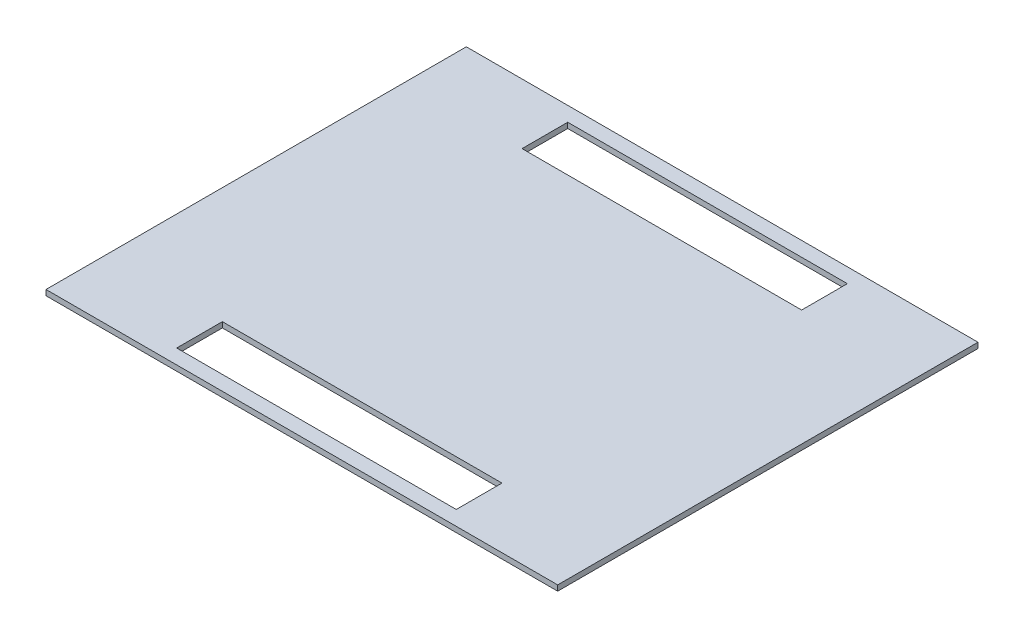
SolidWorks part; units mm, degrees
ref_plane "Front Plane" through (0, 0, 0) normal (0, 0, 1) x (1, 0, 0)
ref_plane "Top Plane" through (0, 0, 0) normal (0, 1, 0) x (1, 0, 0)
ref_plane "Right Plane" through (0, 0, 0) normal (1, 0, 0) x (0, 0, -1)
sketch "Sketch1" plane through (0, 0, 0) normal (0, 1, 0) x (1, 0, 0)
  line L1 (0, 0) -> (-280, 0)
  line L2 (0, 0) -> (0, 230)
  line L3 (0, 230) -> (-280, 230)
  line L4 (-280, 0) -> (-280, 230)
  dimension "D1" = 280
  dimension "D2" = 230
extrude "Boss-Extrude1" add sketch "Sketch1" along normal blind 3
sketch "Sketch4" plane through (0, 3, 0) normal (0, 1, 0) x (1, 0, 0)
  line L0 (-140, 230) -> (-140, 222) construction
  line L1 (0, 230) -> (-280, 230) construction
  line L2 (-140, 222) -> (-216.5, 222) construction
  line L3 (-140, 222) -> (-63.5, 222) construction
  line L4 (-63.5, 222) -> (-63.5, 197) construction
  line L5 (-140, 0) -> (-140, 8) construction
  line L6 (-63.5, 222) -> (-216.5, 222)
  line L7 (-63.5, 222) -> (-63.5, 197)
  line L8 (-63.5, 197) -> (-216.5, 197)
  line L9 (-216.5, 222) -> (-216.5, 197)
  line L10 (-280, 0) -> (0, 0) construction
  line L12 (-216.5, 8) -> (-63.5, 8)
  line L13 (-216.5, 8) -> (-216.5, 33)
  line L14 (-216.5, 33) -> (-63.5, 33)
  line L15 (-63.5, 8) -> (-63.5, 33)
  dimension "D1" = 8
  dimension "D2" = 76.5
  dimension "D3" = 76.5
  dimension "D4" = 25
  dimension "D5" = 8
  dimension "D6" = 25
extrude "Cut-Extrude2" cut sketch "Sketch4" against normal through all
